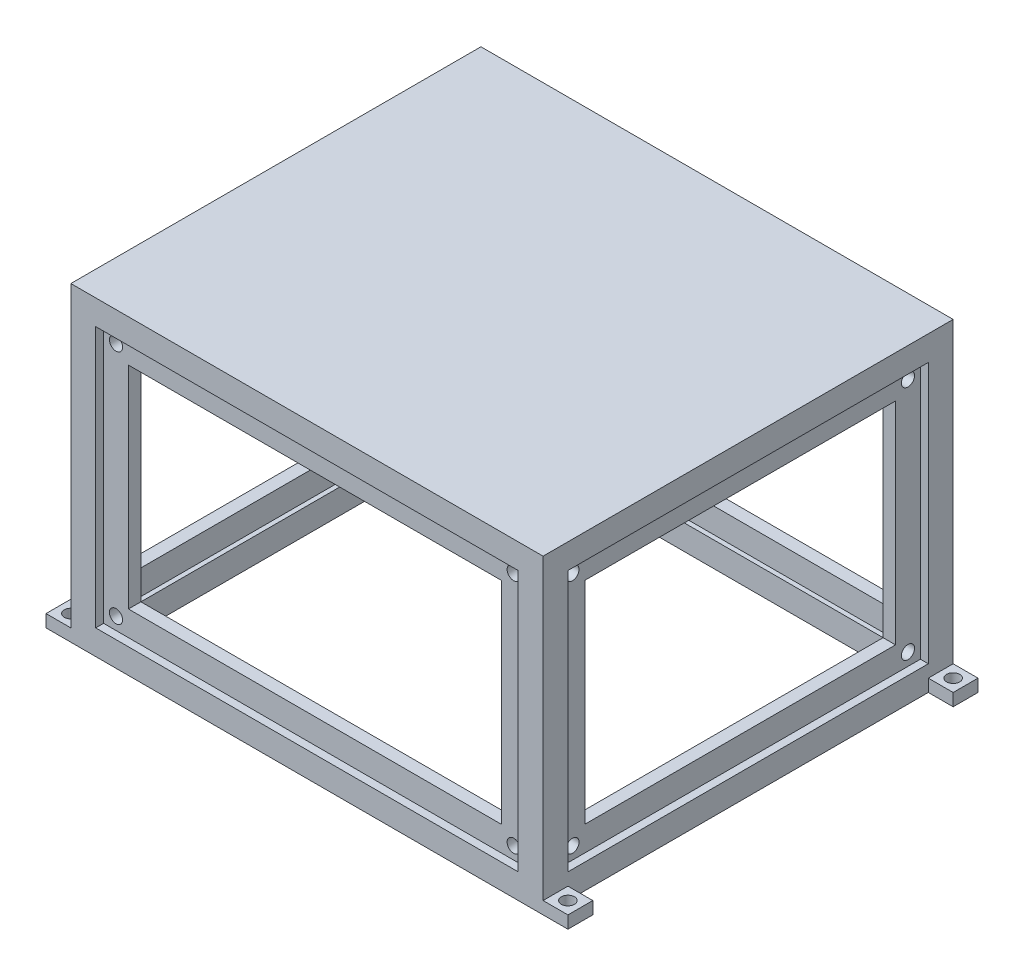
SolidWorks part; units mm, degrees
ref_plane "Plan de face" through (0, 0, 0) normal (0, 0, 1) x (1, 0, 0)
ref_plane "Plan de dessus" through (0, 0, 0) normal (0, 1, 0) x (1, 0, 0)
ref_plane "Plan de droite" through (0, 0, 0) normal (1, 0, 0) x (0, 0, -1)
sketch "Sketch1" plane through (0, 0, 0) normal (0, 1, 0) x (1, 0, 0)
  line L1 (95, -82.5) -> (-95, -82.5)
  line L2 (95, -82.5) -> (95, 82.5)
  line L3 (95, 82.5) -> (-95, 82.5)
  line L4 (-95, -82.5) -> (-95, 82.5)
  line L5 (95, -82.5) -> (-95, 82.5) construction
  line L6 (95, 82.5) -> (-95, -82.5) construction
  point P0 (0, 0)
  dimension "D1" = 165
  dimension "D2" = 190
extrude "Boss-Extrude1" add sketch "Sketch1" along normal blind 125
sketch "Sketch2" plane through (0, 0, 0) normal (0, -1, 0) x (1, 0, 0)
  line L0 (-95, -82.5) -> (-95, 82.5) construction
  line L1 (85, -72.5) -> (-85, -72.5)
  line L2 (85, -72.5) -> (85, 72.5)
  line L3 (85, 72.5) -> (-85, 72.5)
  line L4 (-85, -72.5) -> (-85, 72.5)
  line L5 (85, -72.5) -> (-85, 72.5) construction
  line L6 (85, 72.5) -> (-85, -72.5) construction
  line L7 (-95, 82.5) -> (95, 82.5) construction
  point P0 (0, 0)
  dimension "D1" = 10
  dimension "D2" = 10
extrude "Cut-Extrude1" cut sketch "Sketch2" against normal blind 115
sketch "Sketch3" plane through (-95, 0, 0) normal (-1, 0, 0) x (0, 0, 1)
  line L1 (82.5, 0) -> (72.5, 0)
  line L2 (82.5, 0) -> (82.5, 5)
  line L3 (82.5, 5) -> (72.5, 5)
  line L4 (72.5, 0) -> (72.5, 5)
  dimension "D1" = 10
  dimension "D2" = 5
extrude "Boss-Extrude2" add sketch "Sketch3" along normal blind 10
sketch "Sketch4" plane through (0, 0, 82.5) normal (0, 0, 1) x (1, 0, 0)
  line L0 (-95, 125) -> (-95, 5) construction
  line L1 (85, 10) -> (-85, 10)
  line L2 (85, 10) -> (85, 115)
  line L3 (85, 115) -> (-85, 115)
  line L4 (-85, 10) -> (-85, 115)
  line L5 (85, 10) -> (-85, 115) construction
  line L6 (85, 115) -> (-85, 10) construction
  line L7 (-95, 125) -> (95, 125) construction
  line L8 (0, 0) -> (0, 125) construction
  point P0 (0, 62.5)
  point P9 (0, 0)
  point P13 (0, 62.5)
  dimension "D1" = 10
  dimension "D2" = 10
extrude "Cut-Extrude2" cut sketch "Sketch4" against normal blind 10
sketch "Sketch5" plane through (0, 0, 82.5) normal (0, 0, 1) x (1, 0, 0)
  line L0 (0, 0) -> (0, 125) construction
  line L1 (75, 20) -> (-75, 20)
  line L2 (75, 20) -> (75, 105)
  line L3 (75, 105) -> (-75, 105)
  line L4 (-75, 20) -> (-75, 105)
  line L5 (75, 20) -> (-75, 105) construction
  line L6 (75, 105) -> (-75, 20) construction
  line L7 (90, 5) -> (-90, 5)
  line L8 (90, 5) -> (90, 120)
  line L9 (90, 120) -> (-90, 120)
  line L10 (-90, 5) -> (-90, 120)
  line L11 (90, 5) -> (-90, 120) construction
  line L12 (90, 120) -> (-90, 5) construction
  line L14 (-95, 125) -> (95, 125) construction
  line L15 (-95, 125) -> (-95, 5) construction
  point P0 (0, 62.5)
  point P5 (0, 62.5)
  point P12 (0, 0)
  point P16 (0, 62.5)
  point P17 (0, 0)
  dimension "D1" = 15
  dimension "D2" = 15
  dimension "D3" = 5
  dimension "D4" = 5
extrude "Boss-Extrude3" add sketch "Sketch5" against normal blind 5 from offset 3.175 offset against normal yes
sketch "Sketch6" plane through (0, 5, 0) normal (0, 1, 0) x (1, 0, 0)
  line L0 (-105, -82.5) -> (-105, -72.5) construction
  line L1 (-105, -72.5) -> (-95, -72.5) construction
  circle A0 centre (-100, -77.5) radius 2.65
  dimension "D3" = 5.3
  dimension "D1" = 5
  dimension "D2" = 5
extrude "Cut-Extrude3" cut sketch "Sketch6" against normal blind 5
mirror "Mirror1" about plane through (0, 0, 0) normal (0, 0, 1) of "Boss-Extrude3", "Cut-Extrude2"
mirror "Mirror2" about plane through (0, 0, 0) normal (0, 0, 1) of "Cut-Extrude3", "Boss-Extrude2"
sketch "Sketch7" plane through (-95, 0, 0) normal (-1, 0, 0) x (0, 0, 1)
  line L0 (-82.5, 125) -> (82.5, 125) construction
  line L1 (72.5, 10) -> (-72.5, 10)
  line L2 (72.5, 10) -> (72.5, 115)
  line L3 (72.5, 115) -> (-72.5, 115)
  line L4 (-72.5, 10) -> (-72.5, 115)
  line L5 (72.5, 10) -> (-72.5, 115) construction
  line L6 (72.5, 115) -> (-72.5, 10) construction
  line L7 (82.5, 125) -> (82.5, 5) construction
  line L8 (0, 0) -> (0, 125) construction
  point P0 (0, 62.5)
  point P12 (0, 62.5)
  dimension "D1" = 10
  dimension "D2" = 10
extrude "Cut-Extrude4" cut sketch "Sketch7" against normal blind 10
sketch "Sketch8" plane through (-95, 0, 0) normal (-1, 0, 0) x (0, 0, 1)
  line L0 (-82.5, 125) -> (-82.5, 5) construction
  line L1 (77.5, 5) -> (-77.5, 5)
  line L2 (77.5, 5) -> (77.5, 120)
  line L3 (77.5, 120) -> (-77.5, 120)
  line L4 (-77.5, 5) -> (-77.5, 120)
  line L5 (77.5, 5) -> (-77.5, 120) construction
  line L6 (77.5, 120) -> (-77.5, 5) construction
  line L7 (62.5, 20) -> (-62.5, 20)
  line L8 (62.5, 20) -> (62.5, 105)
  line L9 (62.5, 105) -> (-62.5, 105)
  line L10 (-62.5, 20) -> (-62.5, 105)
  line L11 (62.5, 20) -> (-62.5, 105) construction
  line L12 (62.5, 105) -> (-62.5, 20) construction
  line L13 (-82.5, 125) -> (82.5, 125) construction
  line L14 (0, 0) -> (0, 125) construction
  point P0 (0, 62.5)
  point P5 (0, 62.5)
  point P10 (0, 62.5)
  dimension "D1" = 5
  dimension "D2" = 5
  dimension "D3" = 15
  dimension "D4" = 15
extrude "Boss-Extrude4" add sketch "Sketch8" against normal blind 5 from offset 3.175 offset against normal yes
mirror "Mirror3" about plane through (0, 0, 0) normal (1, 0, 0) of "Boss-Extrude4", "Cut-Extrude4", "Mirror2"
sketch "Sketch9" plane through (-91.825, 0, 0) normal (-1, 0, 0) x (0, 0, 1)
  line L0 (-72.5, 115) -> (-72.5, 10) construction
  line L1 (62.5, 105) -> (-62.5, 105) construction
  line L2 (-62.5, 20) -> (62.5, 20) construction
  circle A0 centre (-67.5, 110) radius 2.65
  circle A1 centre (-67.5, 15) radius 2.65
  point P10 (-59.362, 20)
  dimension "D3" = 5.3
  dimension "D6" = 5.3
  dimension "D1" = 5
  dimension "D2" = 5
  dimension "D4" = 5
  dimension "D5" = 5
extrude "Cut-Extrude5" cut sketch "Sketch9" against normal through all
mirror "Mirror4" about plane through (0, 0, 0) normal (0, 0, 1) of "Cut-Extrude5"
sketch "Sketch10" plane through (0, 0, -79.325) normal (0, 0, -1) x (-1, 0, 0)
  line L0 (-85, 10) -> (-85, 115) construction
  line L1 (-85, 10) -> (-85, 115) construction
  line L2 (-85, 115) -> (85, 115) construction
  line L3 (-85, 10) -> (85, 10) construction
  circle A0 centre (-80, 110) radius 2.65
  circle A1 centre (-80, 15) radius 2.65
  dimension "D5" = 5.3
  dimension "D6" = 5.3
  dimension "D1" = 5
  dimension "D2" = 5
  dimension "D3" = 5
  dimension "D4" = 5
extrude "Cut-Extrude6" cut sketch "Sketch10" against normal through all
mirror "Mirror5" about plane through (0, 0, 0) normal (1, 0, 0) of "Cut-Extrude6"
